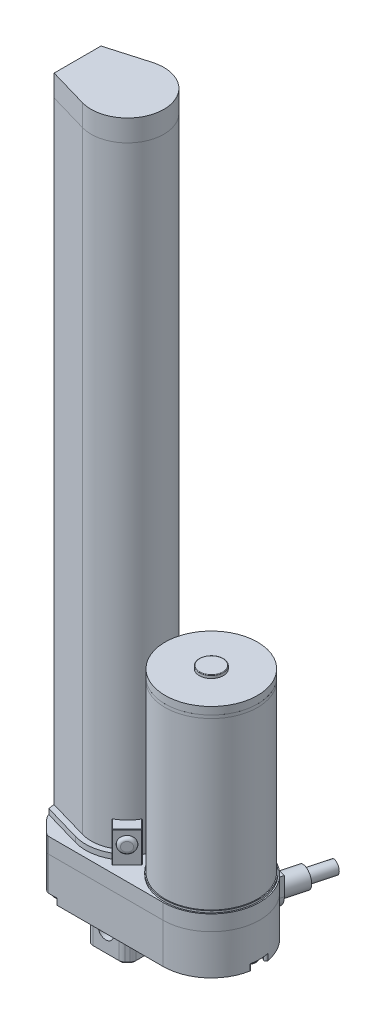
SolidWorks part; units mm, degrees
note: The reader was unsure of these and kept them because the rebuilt part matched: shared geometry of "Sketch1<3>", "Sketch41<11>", "Sketch41<12>", "Sketch45<3>".
ref_plane "Front Plane" through (0, 0, 0) normal (0, 0, 1) x (1, 0, 0)
ref_plane "Top Plane" through (0, 0, 0) normal (0, 1, 0) x (1, 0, 0)
ref_plane "Right Plane" through (0, 0, 0) normal (1, 0, 0) x (0, 0, -1)
sketch "Sketch1" plane through (0, 0, 0) normal (0, 1, 0) x (1, 0, 0)
  line L0 (0, 32.639) -> (7.239, 39.878)
  line L1 (7.239, 0) -> (55.118, 0)
  line L2 (0, 7.239) -> (0, 32.639)
  line L3 (7.239, 39.878) -> (55.118, 39.878)
  line L4 (7.239, 0) -> (0, 7.239)
  arc A0 (55.118, 0) -> (55.118, 39.878) centre (55.118, 19.939) ccw
  point P0 (0, 0)
  point P2 (0, 39.878)
  dimension "D1" = 55.118
  dimension "D2" = 39.878
extrude "Boss-Extrude1" add sketch "Sketch1" along normal blind 6.35
sketch "Sketch6" plane through (0, 6.35, 0) normal (0, 1, 0) x (1, 0, 0)
  circle A0 centre (55.118, 19.939) radius 19.431
extrude "Boss-Extrude4" add sketch "Sketch6" along normal blind 0.762 separate body contours A0
sketch "Sketch7" plane through (0, 7.112, 0) normal (0, 1, 0) x (1, 0, 0)
  circle A0 centre (55.118, 19.939) radius 19.05
  dimension "D1" = 38.1
extrude "Boss-Extrude5" add sketch "Sketch7" along normal blind 68.326 separate body
sketch "Sketch8" plane through (0, 75.438, 0) normal (0, 1, 0) x (1, 0, 0)
  circle A0 centre (55.118, 19.939) radius 4.953
  dimension "D1" = 9.906
fillet "Fillet6" radius 5.08 2 edges at (0, 3.175, -7.239) (0, 3.175, -32.639)
fillet "Fillet7" radius 1.905 2 edges at (7.239, 3.175, -39.878) (7.239, 3.175, 0)
sketch "Sketch15" plane through (0, 6.35, 0) normal (0, 1, 0) x (1, 0, 0)
  line L0 (35.5603, 29.0153) -> (35.5603, 29.0265)
  line L2 (0, 30.5348) -> (0, 9.3432) construction
  line L3 (0, 19.939) -> (0, 10.2869)
  line L4 (0, 19.939) -> (0, 29.591)
  line L5 (0, 10.2869) -> (16.412, 5.5423)
  line L7 (35.5603, 10.8628) -> (35.5603, 10.8515)
  line L10 (0, 29.591) -> (16.4119, 34.3357)
  arc A0 (16.412, 5.5423) -> (16.4119, 34.3357) centre (20.574, 19.939) ccw
ref_plane "Plane4" through (13.8375, 0, -51.6424) normal (0.2588, 0, -0.9659) x (0, -1, 0)
ref_plane "Plane5" through (12.5227, 0, -46.7355) normal (0.2588, 0, -0.9659) x (0, -1, 0)
sketch "Sketch23" plane through (12.5227, 0, -46.7355) normal (0.2588, 0, -0.9659) x (0, -1, 0)
  line L0 (-6.35, -67.5103) -> (-6.35, -28.6483) construction
  line L1 (-2.032, -53.8839) -> (5.588, -53.8839)
  line L2 (-2.032, -53.8839) -> (-2.032, -42.4539)
  line L3 (-2.032, -42.4539) -> (5.588, -42.4539)
  arc A0 (5.588, -53.8839) -> (5.588, -42.4539) centre (5.588, -48.1689) ccw
  dimension "D1" = 11.43
  dimension "D2" = 7.62
  dimension "D3" = 4.318
extrude "Boss-Extrude15" add sketch "Sketch23" along normal blind 6.35
sketch "Sketch24" plane through (14.1662, 0, -52.8692) normal (0.2588, 0, -0.9659) x (-0.9659, 0, -0.2588)
  circle A0 centre (-48.1689, -5.588) radius 4.064
  dimension "D1" = 8.128
extrude "Boss-Extrude16" add sketch "Sketch24" along normal blind 10.16
sketch "Sketch25" plane through (16.7959, 0, -62.683) normal (0.2588, 0, -0.9659) x (-0.9659, 0, -0.2588)
  circle A0 centre (-48.1689, -5.588) radius 2.54
  dimension "D1" = 5.08
extrude "Boss-Extrude17" add sketch "Sketch25" along normal blind 10.16
extrude "Boss-Extrude19" add sketch "Sketch1<3>" against normal blind 16.51 separate body
sketch "Sketch1<3>" plane through (0, 0, 0) normal (0, 1, 0) x (1, 0, 0) same geometry as "Sketch1"
fillet "Fillet13" radius 1.905 2 edges at (7.239, -8.255, 0) (7.239, -8.255, -39.878)
fillet "Fillet14" radius 5.08 2 edges at (0, -8.255, -32.639) (0, -8.255, -7.239)
sketch "Sketch26" plane through (0, -16.51, 0) normal (0, -1, 0) x (-1, 0, 0)
  line L4 (-20.574, 28.829) -> (-11.684, 28.829)
  line L5 (-20.574, 28.829) -> (-29.464, 28.829)
  line L6 (-11.684, 28.829) -> (-11.684, 11.049)
  line L7 (-11.684, 11.049) -> (-29.464, 11.049)
  line L8 (-29.464, 11.049) -> (-29.464, 28.829)
extrude "Boss-Extrude20" add sketch "Sketch26" along normal blind 18.796 separate body
chamfer "Chamfer1" distance 2.54 angle 45 4 edges at (29.464, -25.908, -28.829) (29.464, -25.908, -11.049) (11.684, -25.908, -11.049) (11.684, -25.908, -28.829)
fillet "Fillet15" radius 2.54 8 edges at (11.684, -25.908, -13.589) (14.224, -25.908, -11.049) (26.924, -25.908, -11.049) (29.464, -25.908, -13.589) (29.464, -25.908, -26.289) (26.924, -25.908, -28.829) (11.684, -25.908, -26.289) (14.224, -25.908, -28.829)
chamfer "Chamfer2" distance 0.762 angle 45 16 edges at (14.3041, -35.306, -11.2423) (20.574, -35.306, -11.049) (26.8439, -35.306, -11.2423) (28.194, -35.306, -12.319) (29.2707, -35.306, -13.6691) (29.464, -35.306, -19.939) (29.2707, -35.306, -26.2089) (28.194, -35.306, -27.559) (26.8439, -35.306, -28.6357) (20.574, -35.306, -28.829) (14.3041, -35.306, -28.6357) (12.954, -35.306, -27.559) (11.8773, -35.306, -26.2089) (11.684, -35.306, -19.939) (11.8773, -35.306, -13.6691) (12.954, -35.306, -12.319)
sketch "Sketch27" plane through (0, 0, -11.049) normal (0, 0, 1) x (1, 0, 0)
  circle A0 centre (20.574, -26.67) radius 3.175
extrude "Cut-Extrude3" cut sketch "Sketch27" against normal blind 19.05
sketch "Sketch28" plane through (0, 75.438, 0) normal (0, 1, 0) x (1, 0, 0)
  circle A0 centre (55.118, 19.939) radius 19.05
extrude "Boss-Extrude22" add sketch "Sketch28" along normal blind 1.27 separate body
sketch "Sketch29" plane through (0, 76.708, 0) normal (0, 1, 0) x (1, 0, 0)
  circle A0 centre (55.118, 19.939) radius 19.05
extrude "Boss-Extrude24" add sketch "Sketch29" along normal blind 3.048 separate body contours A0
extrude "Boss-Extrude25" add sketch "Sketch8" along normal blind 1.27 from surface at 4.318 contours A0 starting at face at (55.118, 79.756, -0.889)
fillet "Fillet16" radius 0.2286 1 edges at (55.118, 81.026, -14.986)
extrude "Boss-Extrude26" add sketch "Sketch15" along normal blind 254.381 separate body contours L5 A0 L10 L4 L3
sketch "Sketch32" plane through (0, 260.731, 0) normal (0, 1, 0) x (1, 0, 0)
  line L0 (0, 10.2869) -> (0, 29.591)
  line L1 (0, 29.591) -> (16.4119, 34.3357)
  line L2 (0, 10.2869) -> (16.412, 5.5423)
  arc A0 (16.412, 5.5423) -> (16.4119, 34.3357) centre (20.574, 19.939) ccw
extrude "Boss-Extrude27" add sketch "Sketch32" along normal blind 8.89 separate body
sketch "Sketch33" plane through (0, 269.621, 0) normal (0, 1, 0) x (1, 0, 0)
  circle A0 centre (20.574, 19.939) radius 9.906
extrude "Boss-Extrude28" add sketch "Sketch33" along normal blind 21.336
sketch3d "3DSketch1" plane through (0, 0, 0) normal (0, 0, 1) x (1, 0, 0)
sketch "Sketch41" plane through (0, 6.35, 0) normal (0, 1, 0) x (1, 0, 0)
  line L0 (16.4119, 34.3357) -> (0, 29.591)
  line L1 (37.5429, 9.0662) -> (33.7712, 12.8379)
  line L2 (0.2737, 32.0497) -> (15.777, 36.5318)
  line L3 (37.5429, 9.0662) -> (31.2567, 2.78)
  line L4 (0, 29.591) -> (0, 30.5348)
  line L5 (0, 30.5348) -> (0.2737, 32.0497)
  line L6 (-0.6349, 31.7871) -> (15.777, 36.5318) construction
  line L7 (0, 19.9389) -> (7.9017, 19.9389)
  line L8 (31.2567, 2.78) -> (27.426, 6.6107)
  line L9 (0, 10.2869) -> (0, 29.591) construction
  line L10 (0, 10.2869) -> (0, 9.3431)
  line L12 (37.5429, 30.8116) -> (33.7712, 27.0399)
  line L13 (37.5429, 30.8116) -> (31.2567, 37.0978)
  line L14 (31.2567, 37.0978) -> (27.426, 33.2671)
  line L15 (0, 9.3431) -> (0.2737, 7.8281)
  line L16 (0.2737, 7.8281) -> (15.777, 3.3461)
  line L17 (16.4119, 5.5422) -> (0, 10.2869)
  line L18 (-0.6349, 8.0908) -> (15.7771, 3.3462) construction
  line L19 (27.426, 33.2671) -> (29.1122, 34.9533)
  line L20 (0, 29.591) -> (16.4119, 34.3357) construction
  line L21 (0, 10.2869) -> (16.412, 5.5423) construction
  arc A0 (16.4119, 34.3357) -> (33.7712, 27.0399) centre (20.574, 19.939) cw
  arc A1 (15.777, 36.5318) -> (29.1122, 34.9533) centre (20.574, 19.939) cw
  arc A2 (16.4119, 34.3357) -> (16.412, 5.5423) centre (20.574, 19.939) cw construction
  arc A3 (15.777, 36.5318) -> (15.7771, 3.3462) centre (20.574, 19.939) cw construction
  arc A4 (16.4119, 34.3357) -> (27.426, 33.2671) centre (20.574, 19.939) cw
  arc A5 (15.777, 3.3461) -> (29.1122, 4.9245) centre (20.574, 19.9389) ccw
  arc A6 (16.4119, 5.5422) -> (33.7712, 12.8379) centre (20.574, 19.9389) ccw
  line M5 (0, 30.5348) -> (0, 9.3432)
  arc M6 (0, 9.3432) -> (1.4879, 5.7511) centre (5.08, 9.3432) ccw
extrude "Boss-Extrude30" add sketch "Sketch41" along normal blind 2.159 separate body contours A1 L2 L5 L0 A0 L14 M5
extrude "Boss-Extrude31" add sketch "Sketch41<11>" along normal blind 2.159 separate body contours A6 L17 L15 L16 A5 L8 M5 M6
sketch "Sketch41<11>" plane through (0, 6.35, 0) normal (0, 1, 0) x (1, 0, 0) same geometry as "Sketch41"
extrude "Boss-Extrude33" add sketch "Sketch41<12>" along normal blind 12.7 separate body contours L14 A0 L12 L13 | A6 L8 L3 L1
sketch "Sketch41<12>" plane through (0, 6.35, 0) normal (0, 1, 0) x (1, 0, 0) same geometry as "Sketch41"
fillet "Fillet17" radius 0.2286 5 edges at (35.657, 19.05, -28.9258) (29.3413, 19.05, -35.1825) (34.3998, 19.05, -33.9547) (37.5429, 12.7, -30.8116) (31.2567, 12.7, -37.0978)
fillet "Fillet18" radius 0.2286 5 edges at (35.657, 19.05, -10.9521) (29.3413, 19.05, -4.6954) (37.5429, 12.7, -9.0662) (34.3998, 19.05, -5.9231) (31.2567, 12.7, -2.78)
sketch "Sketch43" plane through (34.1773, 0, -34.1773) normal (0.7071, 0, -0.7071) x (-0.7071, 0, -0.7071)
  circle A0 centre (-0.3147, 13.7414) radius 3.175
extrude "Boss-Extrude34" add sketch "Sketch43" along normal blind 1.27 separate body
fillet "Fillet19" radius 1.27 1 edges at (33.0527, 13.7414, -37.0978)
sketch "Sketch44" plane through (14.2383, 0, 14.2383) normal (0.7071, 0, 0.7071) x (0.7071, 0, -0.7071)
  circle A0 centre (28.5126, 13.7414) radius 3.175
extrude "Boss-Extrude35" add sketch "Sketch44" along normal blind 1.27 separate body
fillet "Fillet20" radius 1.27 1 edges at (37.5429, 13.7414, -7.2702)
sketch "Sketch45" plane through (0, -16.51, 0) normal (0, -1, 0) x (1, 0, 0)
  line L0 (4.0845, -36.7235) -> (6.681, -39.32)
  line L2 (6.681, -39.32) -> (1.4879, -34.1269) construction
  line L4 (55.118, -39.878) -> (8.0281, -39.878) construction
  line L5 (11.3938, -39.878) -> (8.0281, -39.878)
  line L6 (11.3938, 0) -> (8.0281, 0)
  line L7 (4.0845, -3.1545) -> (6.681, -0.558)
  arc A0 (11.2821, -38.9146) -> (11.3938, -39.878) centre (11.8197, -39.3405) ccw
  arc A1 (11.2821, -38.9146) -> (5.0443, -35.9783) centre (8.8543, -35.9783) ccw
  arc A2 (11.2821, -0.9634) -> (11.3938, 0) centre (11.8197, -0.5375) cw
  arc A3 (5.0443, -35.9783) -> (4.0845, -36.7235) centre (4.1918, -35.871) cw
  arc A4 (5.0443, -3.8997) -> (4.0845, -3.1545) centre (4.1918, -4.007) ccw
  arc A5 (11.2821, -0.9634) -> (5.0443, -3.8997) centre (8.8543, -3.8997) cw
  arc A6 (55.118, -39.878) -> (55.118, 0) centre (55.118, -19.939) ccw construction
  arc A7 (73.6621, -16.9922) -> (73.6621, -22.8858) centre (71.247, -19.939) ccw
  arc A8 (73.6621, -22.8858) -> (74.7121, -23.6317) centre (73.8141, -23.7837) cw
  arc A9 (73.6621, -16.9922) -> (74.7121, -16.2463) centre (73.8141, -16.0943) ccw
  arc A10 (8.0281, -39.878) -> (6.681, -39.32) centre (8.0281, -37.973) cw
  arc A11 (8.0281, 0) -> (6.681, -0.558) centre (8.0281, -1.905) ccw
  arc A12 (74.7121, -23.6317) -> (74.7121, -16.2463) centre (55.118, -19.939) ccw
  line M8 (1.4879, -34.1269) -> (6.681, -39.32)
  arc M9 (6.681, -39.32) -> (8.0281, -39.878) centre (8.0281, -37.973) ccw
  line M10 (8.0281, -39.878) -> (55.118, -39.878)
  line M12 (55.118, 0) -> (8.0281, 0)
  arc M13 (8.0281, 0) -> (6.681, -0.558) centre (8.0281, -1.905) ccw
  line M14 (6.681, -0.558) -> (1.4879, -5.7511)
extrude "Cut-Extrude5" cut sketch "Sketch45" against normal blind 2.54 contours A1 A3 A0 M8 M9 M10 | A5 A2 A4 M12 M13 M14
extrude "Cut-Extrude6" cut sketch "Sketch45<3>" against normal blind 2.54
sketch "Sketch45<3>" plane through (0, -16.51, 0) normal (0, -1, 0) x (1, 0, 0) same geometry as "Sketch45"
sketch "Sketch47" plane through (0, -13.97, 0) normal (0, -1, 0) x (-1, 0, 0)
  circle A0 centre (-8.8543, 35.9783) radius 2.54
  circle A1 centre (-8.8543, 3.8997) radius 2.54
  circle A2 centre (-71.247, 19.939) radius 2.54
extrude "Boss-Extrude36" add sketch "Sketch47" along normal blind 2.54 separate body
fillet "Fillet22" radius 1.524 1 edges at (8.8543, -16.51, -38.5183)
fillet "Fillet23" radius 1.524 1 edges at (8.8543, -16.51, -6.4397)
sketch "Sketch48" plane through (0, 0, 0) normal (-1, 0, 0) x (0, 0, 1)
  circle A0 centre (-19.939, 12.7) radius 3.81
extrude "Boss-Extrude37" add sketch "Sketch48" along normal blind 1.524
fillet "Fillet24" radius 1.524 1 edges at (-1.524, 12.7, -16.129)
fillet "Fillet25" radius 1.524 1 edges at (71.247, -16.51, -22.479)
sketch "Sketch49" plane through (0, 0, 0) normal (-1, 0, 0) x (0, 0, 1)
  line L0 (-19.9389, 260.731) -> (-19.9389, 255.778) construction
  line L1 (-29.591, 260.731) -> (-10.2869, 260.731) construction
  line L2 (-30.5348, 6.35) -> (-9.3432, 6.35) construction
  circle A0 centre (-19.9389, 255.778) radius 3.81
  dimension "Flat Head Screw" = 249.428
extrude "Cut-Extrude7" cut sketch "Sketch49" against normal blind 2.54
sketch "Sketch50" plane through (2.54, 0, 0) normal (-1, 0, 0) x (0, 0, 1)
  circle A0 centre (-19.9389, 255.778) radius 3.556
extrude "Boss-Extrude39" add sketch "Sketch50" along normal blind 2.54 contours A0
sketch "Sketch52" plane through (0, 0, -11.049) normal (0, 0, 1) x (1, 0, 0)
  circle A0 centre (20.574, 281.432) radius 3.175
  circle A1 centre (20.574, -26.67) radius 3.175 construction
  dimension "Hole to Hole" = 308.102
extrude "Cut-Extrude11" cut sketch "Sketch52" against normal through all both and the other way through all
sketch "Sketch54" plane through (0, 290.957, 0) normal (0, 1, 0) x (1, 0, 0)
  circle A1 centre (20.574, 19.939) radius 9.906
  circle A2 centre (20.574, 19.939) radius 9.906
  dimension "D1" = 0
extrude "Cut-Extrude12" cut sketch "Sketch54" against normal blind 21.336
equation "\"Stroke\"= 8"
equation "\"D1@Boss-Extrude26\"= \"Stroke\" + 2.015"
equation "\"Flat Head Screw@Sketch49\"= \"Stroke\" + 1.82"
equation "\"Hole to Hole@Sketch52\"= \"Stroke\" + 4.13"
